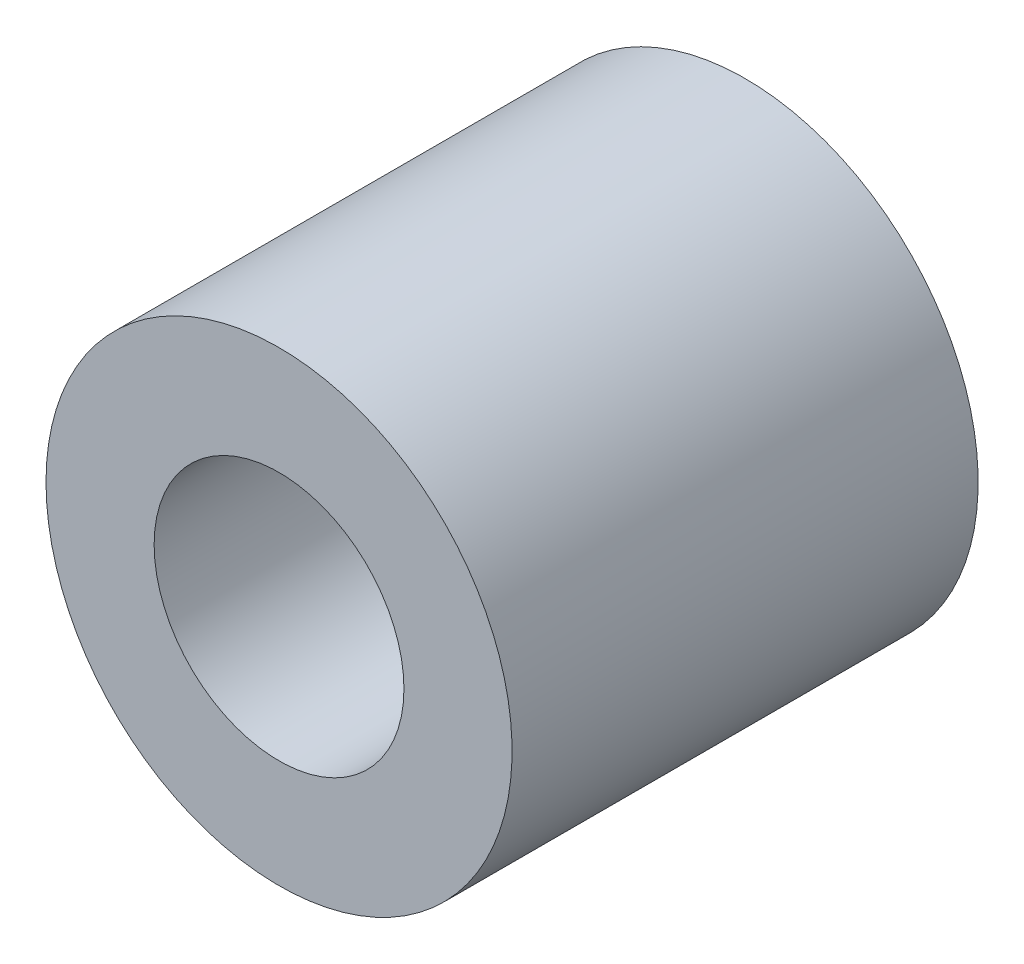
SolidWorks part; units mm, degrees
material "6061-T6 (SS)"
ref_plane "Front Plane" through (0, 0, 0) normal (0, 0, 1) x (1, 0, 0)
ref_plane "Top Plane" through (0, 0, 0) normal (0, 1, 0) x (1, 0, 0)
ref_plane "Right Plane" through (0, 0, 0) normal (1, 0, 0) x (0, 0, -1)
sketch "Sketch1" plane through (0, 0, 0) normal (0, 0, 1) x (1, 0, 0)
  circle A0 centre (0, 0) radius 4.7625
  circle A1 centre (0, 0) radius 2.5527
  dimension "D1" = 9.525
  dimension "D2" = 5.1054
extrude "Boss-Extrude1" add sketch "Sketch1" along normal mid plane 9.525
